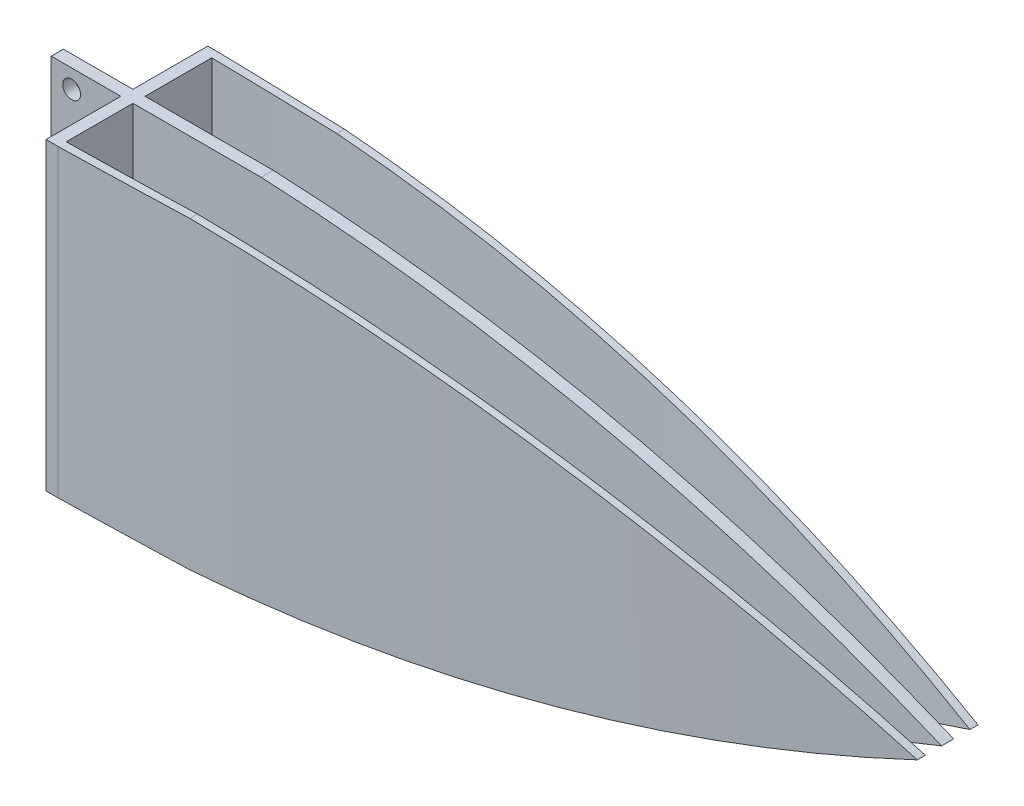
SolidWorks part; units mm, degrees
ref_plane "前基準面" through (0, 0, 0) normal (0, 0, 1) x (1, 0, 0)
ref_plane "上基準面" through (0, 0, 0) normal (0, 1, 0) x (1, 0, 0)
ref_plane "右基準面" through (0, 0, 0) normal (1, 0, 0) x (0, 0, -1)
sketch "草圖1" plane through (0, 0, 0) normal (0, 0, 1) x (1, 0, 0)
  line L0 (-6.5784, -18.2648) -> (-6.5784, 19.7352) construction
  line L4 (0.8982, 19.7352) -> (0.8982, -18.2648)
  line L13 (-4.1018, 17.2352) -> (-9.1018, 17.2352) construction
  line L14 (-4.1018, -15.7648) -> (-9.1018, -15.7648) construction
  line L16 (-9.1018, 19.7352) -> (0.8982, 19.7352)
  line L17 (-9.1018, -18.2648) -> (0.8982, -18.2648)
  line L18 (-9.1018, 19.7352) -> (-9.1018, -18.2648)
  circle A0 centre (-6.6018, -15.7648) radius 1.1
  circle A1 centre (-6.5784, 17.2352) radius 1.1
  dimension "D7" = 2.2
  dimension "D8" = 2.2
  dimension "D1" = 38
  dimension "D2" = 10
extrude "填料-伸長1" add sketch "草圖1" along normal blind 0.75 and the other way blind 0.75
ref_plane "平面1" through (-0.5, 0, 0) normal (1, 0, 0) x (0, 0, -1)
sketch "草圖3" plane through (-0.5, 0, 0) normal (1, 0, 0) x (0, 0, -1)
  line L0 (0, 19.7352) -> (0, -18.3016) construction
  line L1 (-10, 19.7352) -> (10, 19.7352)
  line L2 (-10, 19.7352) -> (-10, -18.3016)
  line L3 (-10, -18.3016) -> (10, -18.3016)
  line L4 (10, 19.7352) -> (10, -18.3016)
  line L5 (-0.75, -18.2648) -> (-0.75, 19.7352) construction
  line L6 (0.75, 19.7352) -> (-0.75, 19.7352) construction
  dimension "D1" = 0.75
  dimension "D2" = 10
  dimension "D3" = 0
extrude "填料-伸長2" add sketch "草圖3" along normal blind 1.5
sketch "草圖4" plane through (0, 0, 0) normal (0, 0, 1) x (1, 0, 0)
  line L2 (1, 19.7352) -> (1, -18.2989)
  line L5 (101, 0.7182) -> (1, 0.7182) construction
  arc A0 (1, 19.7352) -> (101, 0.7182) centre (5.8112, -227.3957) cw
  arc A1 (1, -18.2989) -> (101, 0.7182) centre (5.8112, 228.8321) ccw
  dimension "D1" = 100
extrude "填料-伸長3" add sketch "草圖4" along normal blind 0.75 and the other way blind 0.75
ref_plane "平面2" through (0, 19.7352, 0) normal (0, 1, 0) x (1, 0, 0)
sketch "草圖5" plane through (0, 19.7352, 0) normal (0, 1, 0) x (1, 0, 0)
  line L0 (1, -9) -> (1, -10)
  line L1 (1, -0.75) -> (1, -10) construction
  line L2 (101, -2.75) -> (101, -3.75)
  line L3 (1, 0) -> (101, 0) construction
  line L4 (1, 0.75) -> (1, -0.75) construction
  line L5 (101, 0.75) -> (101, -0.75) construction
  line L6 (101, 2.75) -> (101, 3.75)
  line L7 (1, 9) -> (1, 10)
  arc A0 (1, -9) -> (101, -2.75) centre (-17.2852, 1086.6883) ccw
  arc A1 (101, -3.75) -> (1, -10) centre (-25.1771, 1211.9583) cw
  arc A2 (1, 9) -> (101, 2.75) centre (-17.2852, -1086.6883) cw
  arc A3 (101, 3.75) -> (1, 10) centre (-25.1771, -1211.9583) ccw
  dimension "D2" = 2
  dimension "D1" = 1
  dimension "D3" = 1
extrude "填料-伸長4" add sketch "草圖5" against normal blind 38
ref_plane "平面3" through (0, 0, 10) normal (0, 0, 1) x (1, 0, 0)
sketch "草圖8" plane through (0, 0, 10) normal (0, 0, 1) x (1, 0, 0)
  line L1 (101, -18.2648) -> (101, 19.7011)
  line L2 (1, 0.7182) -> (101, 0.7182) construction
  line L3 (1, 19.7352) -> (1, -18.2989) construction
  line L4 (13.1037, 19.6745) -> (101, 19.7011)
  line L5 (13.1037, -18.2381) -> (101, -18.2648)
  arc A0 (13.1037, -18.2381) -> (101, 0.7182) centre (5.8112, 228.8321) ccw
  arc A1 (1, -18.2989) -> (101, 0.7182) centre (5.8112, 228.8321) ccw construction
  arc A2 (13.1037, 19.6745) -> (101, 0.7182) centre (5.8112, -227.3957) cw
extrude "除料-伸長1" cut sketch "草圖8" against normal blind 20 and the other way blind 10 contours A0 L5 L1 | L4 A2 L1 region at (77.7362, -12.5844, 10) region at (77.7362, 14.0208, 10)
ref_plane "平面4" through (0, 19.7352, 0) normal (0, 1, 0) x (1, 0, 0)
ref_plane "平面5" through (0, 19.7352, 0) normal (0, 1, 0) x (1, 0, 0)
sketch "草圖10" plane through (0, 19.7352, 0) normal (0, 1, 0) x (1, 0, 0)
  line L0 (-22.4534, -10) -> (22.4534, -10) construction
  line L1 (-9.7542, 10.5434) -> (102.7429, 10.5434)
  line L2 (-9.7542, 10.5434) -> (-9.7542, -10)
  line L3 (-9.7542, -10) -> (102.7429, -10)
  line L4 (102.7429, 10.5434) -> (102.7429, -10)
extrude "除料-伸長4" cut sketch "草圖10" against normal blind 0.2 and the other way blind 0.2
ref_plane "平面6" through (0, -18.3016, 0) normal (0, -1, 0) x (-1, 0, 0)
sketch "草圖11" plane through (0, -18.3016, 0) normal (0, -1, 0) x (-1, 0, 0)
  line L0 (-22.4534, -10) -> (22.4534, -10) construction
  line L1 (0.716, -10) -> (-103.7986, -10)
  line L2 (0.716, -10) -> (0.716, 11.6577)
  line L3 (0.716, 11.6577) -> (-103.7986, 11.6577)
  line L4 (-103.7986, -10) -> (-103.7986, 11.6577)
extrude "除料-伸長5" cut sketch "草圖11" against normal blind 0.2 and the other way blind 0.2
